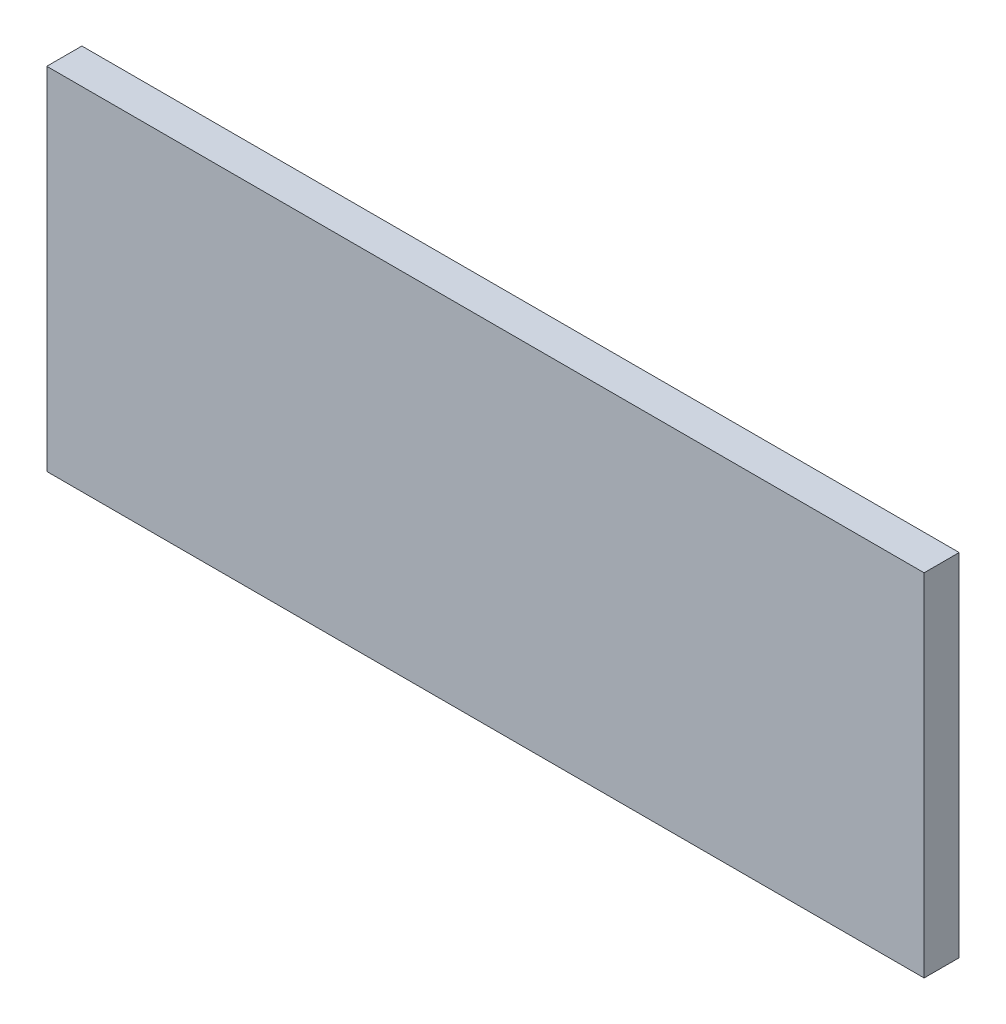
SolidWorks part; units mm, degrees
material "Лист 6,0 ГОСТ 19903-2015 / Ст3сп ГОСТ 14637-89"
ref_plane "Спереди" through (0, 0, 0) normal (0, 0, 1) x (1, 0, 0)
ref_plane "Сверху" through (0, 0, 0) normal (0, 1, 0) x (1, 0, 0)
ref_plane "Справа" through (0, 0, 0) normal (1, 0, 0) x (0, 0, -1)
sketch "Эскиз1" plane through (0, 0, 0) normal (0, 0, 1) x (1, 0, 0)
  line L1 (-75, -30) -> (75, -30)
  line L2 (-75, -30) -> (-75, 30)
  line L3 (-75, 30) -> (75, 30)
  line L4 (75, -30) -> (75, 30)
base flange "Базовая кромка1" sketch "Эскиз1" thickness 6 reverse thickness direction no parameters "D1"=6
sketch "Сгиб-Линии1" [suppressed] plane through (0, 0, 0) normal (0, 1, 0) x (1, 0, 0)
sketch "Граничная рамка1" [suppressed] plane through (0, 0, 0) normal (0, 1, 0) x (1, 0, 0)
sheet metal parameters "Листовой металл30" thickness 6 parameters "D1"=6
flat pattern "Развертка30" [suppressed]
sketch "Сгиб-Линии2" plane through (0, 0, 0) normal (0, 1, 0) x (1, 0, 0)
sketch3d "Граничная рамка2" [suppressed]
  line L0 (75, -30, 0) -> (-75, -30, 0) construction
  line L1 (75, 30, 0) -> (-75, 30, 0) construction
  line L2 (75, -30, 0) -> (75, 30, 0) construction
  line L3 (-75, -30, 0) -> (-75, 30, 0) construction
